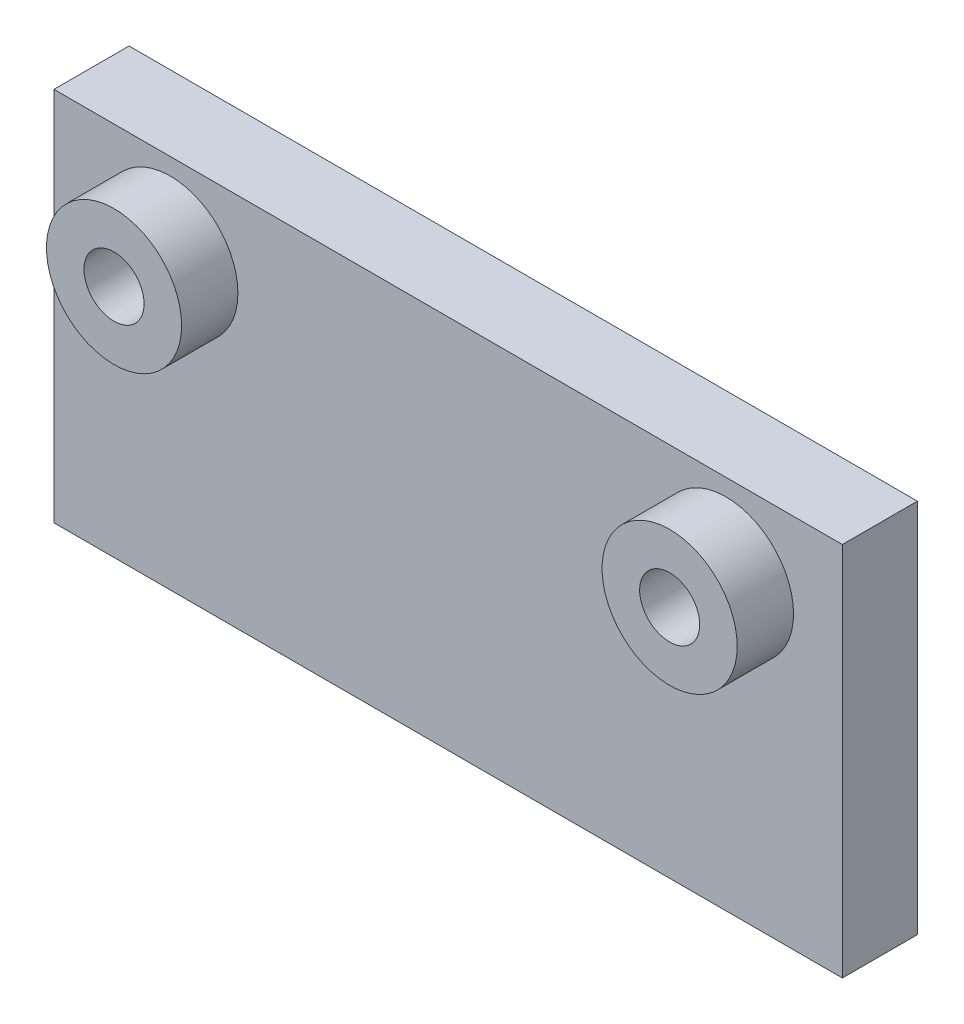
SolidWorks part; units mm, degrees
ref_plane "前视基准面" through (0, 0, 0) normal (0, 0, 1) x (1, 0, 0)
ref_plane "上视基准面" through (0, 0, 0) normal (0, 1, 0) x (1, 0, 0)
ref_plane "右视基准面" through (0, 0, 0) normal (1, 0, 0) x (0, 0, -1)
sketch "草图1" plane through (0, 0, 0) normal (0, 0, 1) x (1, 0, 0)
  line L0 (22.2618, 0) -> (-22.2618, 0) construction
  line L3 (-21, 15) -> (21, 15)
  line L5 (-21, 15) -> (-21, -5)
  line L7 (21, 15) -> (21, -5)
  line L9 (-21, -5) -> (21, -5)
  circle A0 centre (-14.8, 10.5) radius 1.6
  circle A1 centre (14.8, 10.5) radius 1.6
  circle A2 centre (-14.8, 10.5) radius 3.6
  circle A3 centre (14.8, 10.5) radius 3.6
  point P0 (0, 0)
  point P4 (0, 0)
  point P18 (0, 15)
extrude "凸台-拉伸1" add sketch "草图1" along normal blind 4 contours L3 A3 A2 | L7 L0 L5 region at (0, -2.5, 0) region at (0, 7.0547, 0)
extrude "凸台-拉伸2" add sketch "草图1<3>" along normal blind 7 contours A2 A0 | A3 A1 region at (-18.2982, 10.5, 0) region at (11.3018, 10.5, 0)
sketch "草图1<3>" plane through (0, 0, 0) normal (0, 0, 1) x (1, 0, 0) same geometry as "草图1"
sketch "草图6" plane through (0, 0, 0) normal (0, 0, -1) x (-1, 0, 0)
  line L1 (-11.6246, 10.5) -> (-13.2123, 13.25)
  line L2 (-13.2123, 13.25) -> (-16.3877, 13.25)
  line L3 (-16.3877, 13.25) -> (-17.9754, 10.5)
  line L4 (-17.9754, 10.5) -> (-16.3877, 7.75)
  line L5 (-16.3877, 7.75) -> (-13.2123, 7.75)
  line L6 (-13.2123, 7.75) -> (-11.6246, 10.5)
  line L7 (17.9754, 10.5) -> (16.3877, 13.25)
  line L8 (16.3877, 13.25) -> (13.2123, 13.25)
  line L9 (13.2123, 13.25) -> (11.6246, 10.5)
  line L10 (11.6246, 10.5) -> (13.2123, 7.75)
  line L11 (13.2123, 7.75) -> (16.3877, 7.75)
  line L12 (16.3877, 7.75) -> (17.9754, 10.5)
  circle A0 centre (-14.8, 10.5) radius 2.75 construction
  circle A1 centre (14.8, 10.5) radius 2.75 construction
extrude "切除-拉伸3" cut sketch "草图6" against normal blind 2.6
sketch "草图7" plane through (0, 0, 0) normal (0, 0, -1) x (-1, 0, 0)
  line L0 (-8.5, 0) -> (-8.5, -5)
  line L1 (21, -5) -> (-21, -5) construction
  line L2 (8.5, 0) -> (8.5, -5)
  line L3 (-8.5, -5) -> (-8.5, 0)
  line L4 (8.5, 0) -> (-8.5, 0)
  line L5 (-8.5, -5) -> (8.5, -5)
  line M18 (-21, -5) -> (21, -5)
extrude "凸台-拉伸4" add sketch "草图7" along normal blind 8 contours L2 L4 L0 M18 region at (0, -2.5, 0)
sketch "草图8" plane through (0, 0, 0) normal (0, 1, 0) x (1, 0, 0)
  line L0 (5, 0) -> (-5, 0)
  line L1 (-8.5, 0) -> (8.5, 0) construction
  line L2 (-5, 0) -> (-5, 4.6)
  circle A0 centre (-5, 4.6) radius 1.6
  circle A1 centre (5, 4.6) radius 1.6
  point P6 (0, 0)
extrude "切除-拉伸4" cut sketch "草图8" against normal blind 6.6 contours A1 | A0 region at (-3.9006, 0, -3.5006) region at (5, 0, -4.6)
sketch "草图9" plane through (0, 0, 0) normal (0, 1, 0) x (1, 0, 0)
  line L1 (1.8246, 4.6) -> (3.4123, 1.85)
  line L2 (3.4123, 1.85) -> (6.5877, 1.85)
  line L3 (6.5877, 1.85) -> (8.1754, 4.6)
  line L4 (8.1754, 4.6) -> (6.5877, 7.35)
  line L5 (6.5877, 7.35) -> (3.4123, 7.35)
  line L6 (3.4123, 7.35) -> (1.8246, 4.6)
  line L7 (-8.1754, 4.6) -> (-6.5877, 1.85)
  line L8 (-6.5877, 1.85) -> (-3.4123, 1.85)
  line L9 (-3.4123, 1.85) -> (-1.8246, 4.6)
  line L10 (-1.8246, 4.6) -> (-3.4123, 7.35)
  line L11 (-3.4123, 7.35) -> (-6.5877, 7.35)
  line L12 (-6.5877, 7.35) -> (-8.1754, 4.6)
  circle A0 centre (5, 4.6) radius 2.75 construction
  circle A1 centre (-5, 4.6) radius 2.75 construction
extrude "切除-拉伸5" cut sketch "草图9" against normal blind 2.6
equation "\"2.6.00mm\"=10"
